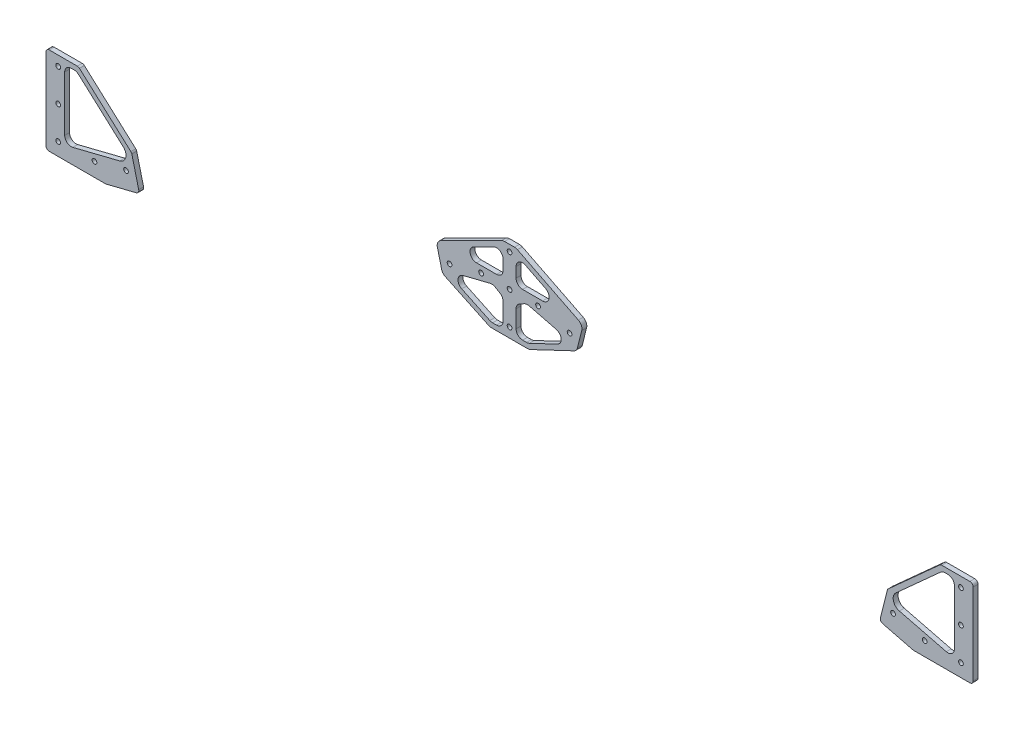
SolidWorks part; units mm, degrees
material "Thornel Mat VMA"
ref_plane "前视基准面" through (0, 0, 0) normal (0, 0, 1) x (1, 0, 0)
ref_plane "上视基准面" through (0, 0, 0) normal (0, 1, 0) x (1, 0, 0)
ref_plane "右视基准面" through (0, 0, 0) normal (1, 0, 0) x (0, 0, -1)
sketch "草图1" plane through (0, 0, 0) normal (0, 0, 1) x (1, 0, 0)
  line L0 (0, 0) -> (277.5, 0) construction
  line L1 (277.5, 0) -> (277.5, 70) construction
  line L2 (0, 0) -> (0, 30) construction
  line L3 (4, 53) -> (4, 10.1231)
  line L4 (260, 70) -> (0, 5) construction
  line L5 (0, 2) -> (-7.5, 2)
  line L6 (-7.5, 2) -> (-7.5, 56)
  line L7 (-7.5, 56) -> (12.5, 56)
  line L8 (12.5, 56) -> (45.1134, 26.5861)
  line L9 (45.1134, 26.5861) -> (49.9641, 7.1833)
  line L10 (49.9641, 7.1833) -> (29.2311, 2)
  line L11 (29.2311, 2) -> (0, 2)
  line L12 (277.5, 44) -> (265.5, 44)
  line L13 (265.5, 44) -> (236.2315, 57.8732)
  line L14 (236.2315, 57.8732) -> (232.3509, 73.3955)
  line L15 (232.3509, 73.3955) -> (273.5, 94)
  line L16 (273.5, 94) -> (281.5, 94)
  line L17 (281.5, 94) -> (281.5, 44)
  line L18 (281.5, 44) -> (277.5, 44)
  line L19 (4, 10.1231) -> (37.8685, 18.5902)
  line L20 (40.0045, 27.1539) -> (11.347, 53)
  line L21 (11.347, 53) -> (4, 53)
  line L22 (273.5, 64) -> (273.5, 47)
  line L23 (273.5, 47) -> (266.175, 47)
  line L24 (266.175, 47) -> (237.9696, 60.3693)
  line L25 (237.9696, 60.3693) -> (267.1522, 67.6649)
  line L26 (267.1522, 67.6649) -> (273.5, 64)
  line L27 (273.5, 90.6449) -> (273.5, 74)
  line L28 (273.5, 74) -> (240.2586, 74)
  line L29 (240.2586, 74) -> (273.5, 90.6449)
  circle A0 centre (0, 30) radius 1.45
  circle A1 centre (0, 10) radius 1.45
  circle A2 centre (0, 50) radius 1.45
  circle A3 centre (22.3151, 10.5788) radius 1.45
  circle A4 centre (41.7179, 15.4295) radius 1.45
  circle A5 centre (277.5, 70) radius 1.45
  circle A6 centre (277.5, 50) radius 1.45
  circle A7 centre (277.5, 90) radius 1.45
  circle A8 centre (260, 70) radius 1.45
  circle A9 centre (240.5971, 65.1493) radius 1.45
  arc A10 (37.8685, 18.5902) -> (40.0045, 27.1539) centre (36.6558, 23.4409) ccw
  dimension "D5" = 2.9
  dimension "D8" = 2.9
  dimension "D10" = 2.9
  dimension "D36" = 5
  dimension "D1" = 277.5
  dimension "D2" = 30
  dimension "D3" = 70
  dimension "D4" = 260
  dimension "D6" = 20
  dimension "D7" = 20
  dimension "D9" = 20
  dimension "D11" = 20
  dimension "D12" = 20
  dimension "D13" = 20
  dimension "D14" = 205
  dimension "D15" = 70
  dimension "D16" = 5
  dimension "D17" = 6
  dimension "D18" = 10
  dimension "D19" = 4
  dimension "D20" = 6
  dimension "D21" = 4
  dimension "D22" = 6
  dimension "D23" = 10
  dimension "D24" = 10
  dimension "D25" = 6
  dimension "D26" = 8
  dimension "D27" = 6
  dimension "D28" = 8
  dimension "D29" = 7.5
  dimension "D30" = 12
  dimension "D31" = 20
  dimension "D32" = 3
  dimension "D33" = 3
  dimension "D34" = 4
  dimension "D35" = 4
  dimension "D37" = 120
  dimension "D38" = 4
  dimension "D39" = 3
  dimension "D40" = 3
  dimension "D41" = 4
  dimension "D42" = 6
  dimension "D43" = 3
  dimension "D44" = 4
extrude "凸台-拉伸1" add sketch "草图1" along normal blind 3
ref_plane "基准面1" through (277.5, 0, 0) normal (-1, 0, 0) x (0, 0, 1)
mirror "镜向4" about plane through (277.5, 0, 0) normal (-1, 0, 0) of bodies 101 102
combine bodies "组合4" operation type add bodies to combine 102 109
fillet "圆角1" radius 4 3 edges at (4, 53, 1.5) (11.347, 53, 1.5) (4, 10.1231, 1.5)
fillet "圆角2" radius 4 16 edges at (314.7414, 74, 1.5) (281.5, 90.6449, 1.5) (281.5, 74, 1.5) (288.825, 47, 1.5) (317.0304, 60.3693, 1.5) (287.8478, 67.6649, 1.5) (281.5, 47, 1.5) (273.5, 90.6449, 1.5) (240.2586, 74, 1.5) (273.5, 74, 1.5) (273.5, 64, 1.5) (267.1522, 67.6649, 1.5) (237.9696, 60.3693, 1.5) (266.175, 47, 1.5) (273.5, 47, 1.5) (281.5, 64, 1.5)
fillet "圆角3" radius 4 3 edges at (543.653, 53, 1.5) (551, 10.1231, 1.5) (551, 53, 1.5)
fillet "圆角4" radius 2 6 edges at (-7.5, 56, 1.5) (12.5, 56, 1.5) (45.1134, 26.5861, 1.5) (49.9641, 7.1833, 1.5) (29.2311, 2, 1.5) (-7.5, 2, 1.5)
fillet "圆角5" radius 2 6 edges at (525.7689, 2, 1.5) (509.8866, 26.5861, 1.5) (542.5, 56, 1.5) (562.5, 56, 1.5) (562.5, 2, 1.5) (505.0359, 7.1833, 1.5)
fillet "圆角6" radius 4 8 edges at (265.5, 44, 1.5) (232.3509, 73.3955, 1.5) (273.5, 94, 1.5) (281.5, 94, 1.5) (322.6491, 73.3955, 1.5) (318.7685, 57.8732, 1.5) (289.5, 44, 1.5) (236.2315, 57.8732, 1.5)
